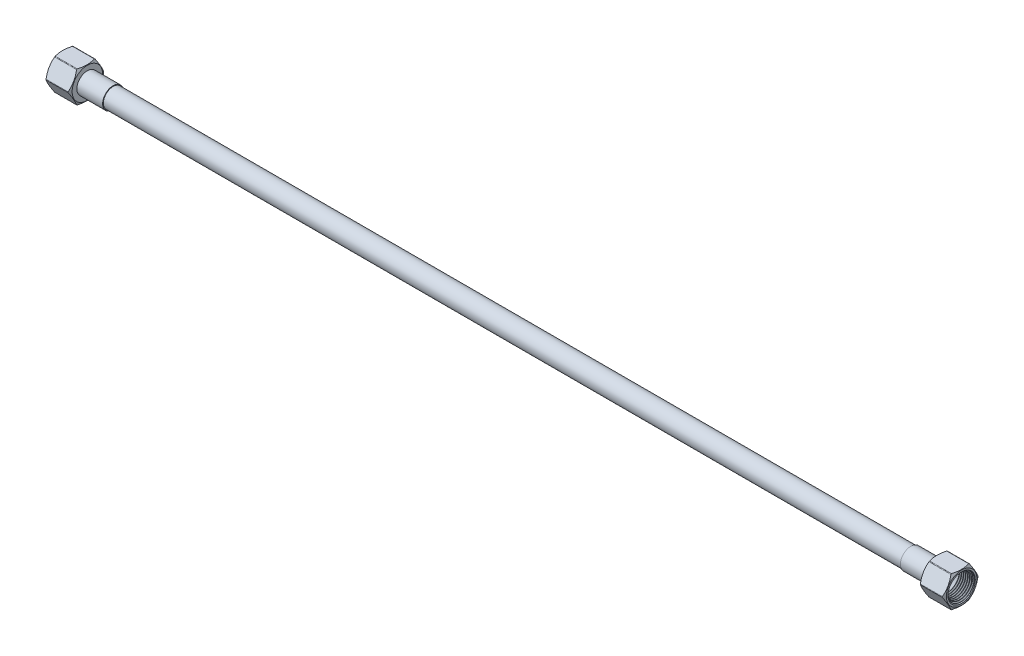
SolidWorks part; units mm, degrees
ref_plane "Front Plane" through (0, 0, 0) normal (0, 0, 1) x (1, 0, 0)
ref_plane "Top Plane" through (0, 0, 0) normal (0, 1, 0) x (1, 0, 0)
ref_plane "Right Plane" through (0, 0, 0) normal (1, 0, 0) x (0, 0, -1)
sketch "Sketch1" plane through (0, 0, 0) normal (0, 0, 1) x (1, 0, 0)
  line L0 (457.2, 0) -> (-457.2, 0) construction
  line L1 (-431.8, -13.4938) -> (-431.8, 13.4937) construction
  line L2 (-431.8, 13.4937) -> (-457.2, 13.4937) construction
  line L3 (0, 9.8806) -> (0, -9.8806) construction
  line L4 (-457.2, 13.4937) -> (-457.2, 0) construction
  line L5 (-431.8, 13.4937) -> (-433.9167, 13.4937) construction
  line L6 (-457.2, 15.875) -> (-431.8, 15.875) construction
  line L7 (-431.8, 10.6426) -> (-405.6063, 10.6426) construction
  line L10 (-431.8, 0) -> (-449.7068, 13.4937) construction
  line L11 (-457.2, -13.4938) -> (-457.2, 13.4937) construction
  line L12 (457.2, 13.4937) -> (457.2, 0) construction
  line L13 (457.2, -13.4937) -> (457.2, 13.4937) construction
  point P3 (-378.6188, 0)
  point P4 (0, 0)
  point P8 (-431.8, 0)
  point P11 (0, 7.9375)
  point P20 (378.6188, 0)
  point P30 (-442.1187, 13.4937)
  point P40 (-457.2, -13.4938)
  point P42 (-457.2, 0)
  point P45 (457.2, 0)
  point P46 (457.2, -13.4937)
  point P47 (-398.8594, -9.8806)
  dimension "Thread Size" = 26.9875
  dimension "OD" = 19.7612
  dimension "ID" = 15.875
  dimension "Pitch" = 2.1167
  dimension "Hex Length" = 25.4
  dimension "Hex Width" = 31.75
  dimension "Length" = 914.4
  dimension "D5" = 26.1937
  dimension "D2" = 0.762
  dimension "D1" = 26.9875
  dimension "Flared Angle" = 37
  dimension "Thread Length" = 15.0812
  dimension "D3" = 6.7469
sketch "Sketch2" plane through (0, 0, 0) normal (1, 0, 0) x (0, 0, -1)
  line L0 (-8.7072, -15.0812) -> (0, 0) construction
  line L1 (8.7072, 15.875) -> (-8.7072, 15.875)
  line L2 (-9.3946, 15.4781) -> (-18.1017, 0.3969)
  line L3 (-18.1017, -0.3969) -> (-9.3946, -15.4781)
  line L4 (-8.7072, -15.875) -> (8.7072, -15.875)
  line L5 (9.3946, -15.4781) -> (18.1017, -0.3969)
  line L6 (18.1017, 0.3969) -> (9.3946, 15.4781)
  circle A0 centre (0, 0) radius 15.875 construction
  arc A1 (8.7072, -15.875) -> (9.3946, -15.4781) centre (8.7072, -15.0812) ccw
  circle A2 centre (0, 0) radius 13.4937
  arc A3 (18.1017, -0.3969) -> (18.1017, 0.3969) centre (17.4143, 0) ccw
  arc A4 (-9.3946, -15.4781) -> (-8.7072, -15.875) centre (-8.7072, -15.0812) ccw
  arc A5 (-18.1017, 0.3969) -> (-18.1017, -0.3969) centre (-17.4143, 0) ccw
  arc A6 (-8.7072, 15.875) -> (-9.3946, 15.4781) centre (-8.7072, 15.0812) ccw
  arc A7 (8.7072, 15.875) -> (9.3946, 15.4781) centre (8.7072, 15.0812) cw
  point P9 (-6.7469, -11.6859)
  dimension "D1" = 0.7937
extrude "Boss-Extrude1" add sketch "Sketch2" along normal up to vertex (-431.8 mm away) from vertex up to point (-431.8, 15.875, 0) starting at point (-457.2, 15.875, 0)
sketch "Sketch3" plane through (-457.2, 0, 0) normal (-1, 0, 0) x (0, 0, 1)
  circle A1 centre (0, 0) radius 15.494
  dimension "D1" = 0.381
extrude "Cut-Extrude1" cut sketch "Sketch3" against normal through all draft 60 flip side to cut
extrude "Cut-Extrude2" cut sketch "Sketch4<2>" along normal through all draft 60 from surface flip side to cut starting at face at (-431.8, 0, 0)
sketch "Sketch4<2>" plane through (-457.2, 0, 0) normal (-1, 0, 0) x (0, 0, 1) same geometry as "Sketch3"
sketch "Sketch4" plane through (-431.8, 0, 0) normal (1, 0, 0) x (0, 0, -1)
  line L0 (0, 9.8806) -> (0, -9.8806) construction
  line L1 (0, 9.8806) -> (0, -9.8806) construction
  circle A0 centre (0, 0) radius 13.4937 construction
  circle A1 centre (0, 0) radius 13.4937
  circle A2 centre (0, 0) radius 10.6426
  point P7 (0, 7.9375)
extrude "Boss-Extrude2" add sketch "Sketch4" against normal blind 1.5875
sketch "Sketch5" plane through (0, 0, 0) normal (0, 0, 1) x (1, 0, 0)
  line L7 (-405.6063, 10.6426) -> (-433.3875, 10.6426)
  line L16 (-431.8, -13.4938) -> (-431.8, 13.4937) construction
  line L17 (-431.8, 0) -> (-449.7068, 13.4937) construction
  line L32 (-433.3875, 10.6426) -> (-433.3875, 13.4937)
  line L33 (-431.8, 13.4937) -> (-457.2, 13.4937) construction
  line L34 (-433.3875, 13.4937) -> (-442.1187, 13.4937)
  line L35 (-442.1187, 13.4937) -> (-442.1187, 13.3667)
  line L36 (-442.1187, 13.3667) -> (-434.9139, 7.9375)
  line L37 (-434.9139, 7.9375) -> (-431.8, 7.9375)
  line L38 (-431.8, 7.9375) -> (-431.8, 9.8806)
  line L39 (-431.8, 9.8806) -> (-405.6063, 9.8806)
  line L40 (-405.6063, 9.8806) -> (-405.6063, 10.6426)
  line L41 (457.2, 0) -> (-457.2, 0) construction
  line L42 (457.2, 0) -> (-457.2, 0) construction
  line L46 (-433.3875, 13.4937) -> (-433.3875, -13.4937) construction
  dimension "D1" = 0.127
  dimension "D3" = 15.0812
revolve "Revolve1" add sketch "Sketch5" angle 360 about L0
mirror "Mirror1" about plane through (0, 0, 0) normal (1, 0, 0) of bodies 144 143
sketch "Sketch6" plane through (-431.8, 0, 0) normal (1, 0, 0) x (0, 0, -1)
  circle A5 centre (0, 0) radius 9.8806
  circle A6 centre (0, 0) radius 7.9375
extrude "Boss-Extrude3" add sketch "Sketch6" along normal up to surface (863.6 mm away) separate body up to face at (431.8, 9.8806, 0)
sketch "Sketch7" plane through (-457.2, 0, 0) normal (-1, 0, 0) x (0, 0, 1)
  circle A0 centre (0, 0) radius 13.4937 construction
  circle A1 centre (0, 0) radius 13.4937
extrude "Boss-Extrude4" add sketch "Sketch7" against normal up to surface (15.0813 mm away) separate body up to face at (-442.1187, 13.3667, 0)
extrude "Boss-Extrude5" add sketch "Sketch8<2>" against normal up to surface (15.0813 mm away) up to face at (-442.1187, 13.3667, 0)
sketch "Sketch8<2>" plane through (-457.2, 0, 0) normal (-1, 0, 0) x (0, 0, 1) same geometry as "Sketch7"
sketch "Sketch8" plane through (-457.2, 0, 0) normal (-1, 0, 0) x (0, 0, 1)
  circle A0 centre (0, 0) radius 13.4937 construction
  circle A1 centre (0, 0) radius 13.4937
curve "Helix/Spiral1" pitch 2.1167 height 17.1979 radius 13.4937 centre (-457.2, 0, 0) axis (1, 0, 0) start towards (0, 1, 0)
sketch "Sketch9" plane through (0, 0, 0) normal (0, 0, 1) x (1, 0, 0)
  line L0 (-459.1844, 13.7229) -> (-458.126, 11.8898) construction
  line L1 (-458.126, 11.8898) -> (-457.0677, 13.7229) construction
  line L2 (-457.0677, 13.7229) -> (-459.1844, 13.7229) construction
  line L3 (-459.0521, 13.4937) -> (-457.2, 13.4937) construction
  line L4 (-458.126, 13.7229) -> (-458.126, 13.4937) construction
  line L5 (-458.126, 13.4937) -> (-458.126, 12.1189) construction
  line L6 (-458.126, 12.1189) -> (-458.126, 11.8898) construction
  line L7 (-458.2583, 12.1189) -> (-457.9938, 12.1189)
  line L8 (-459.1182, 13.6083) -> (-457.1339, 13.6083)
  line L9 (-457.9938, 12.1189) -> (-457.1339, 13.6083)
  line L10 (-458.2583, 12.1189) -> (-459.1182, 13.6083)
  point P12 (-458.126, 13.6083)
  dimension "D1" = 2.1167
  dimension "D2" = 0.2646
sweep "Cut-Sweep1" cut profiles "Sketch9" path "Helix/Spiral1" align with end faces yes
combine bodies "Combine1" operation type subtract main body 149 bodies to subtract 150
sketch "Sketch10" plane through (-457.2, 0, 0) normal (-1, 0, 0) x (0, 0, 1)
  circle A0 centre (0, 0) radius 13.4937 construction
  circle A1 centre (0, 0) radius 13.4937 construction
  circle A2 centre (0, 0) radius 13.8906
  dimension "D1" = 0.3969
extrude "Cut-Extrude3" cut sketch "Sketch10" against normal through all draft 45
delete or keep bodies "Body-Delete/Keep 1" type delete bodies bodies 146
pattern_circular "CirPattern1" count 2 over 360 about axis through (0, 9.8806, 0) along (0, -1, 0) of bodies 152
equation "\"D4@Helix/Spiral1\"=\"Pitch@Sketch1\""
equation "\"D3@Helix/Spiral1\"=\"D3@Sketch5\"+\"Pitch@Sketch1\""
equation "\"D2@Sketch9\" = \"D1@Sketch9\" / 8"
equation "\"D1@Sketch9\" = \"Pitch@Sketch1\""
equation "\"D5@Sketch1\" = \"Hex Length@Sketch1\" + .03125"
equation "\"D1@Sketch1\"=\"Thread Size@Sketch1\""
equation "\"Thread Length@Sketch1\"=\"Hex Length@Sketch1\" * .59375"
equation "\"D3@Sketch1\"=\"D1@Sketch1\"/4"
